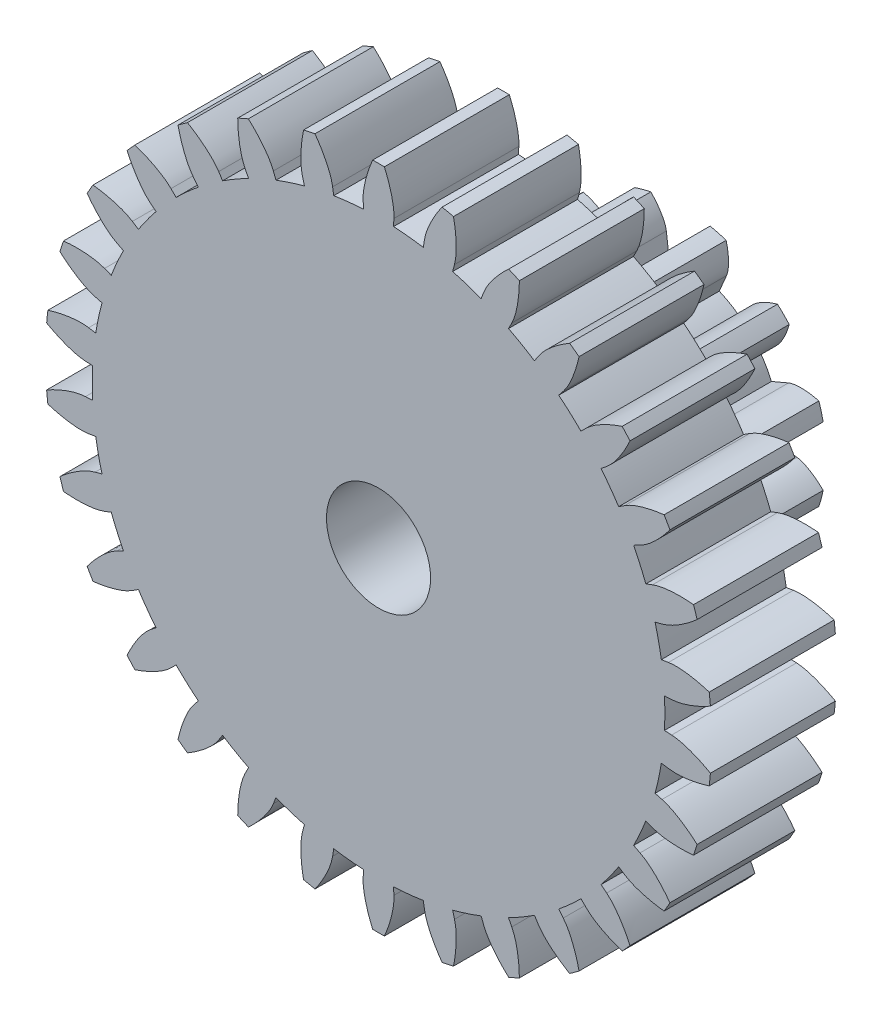
SolidWorks part; units mm, degrees
ref_plane "前视基准面" through (0, 0, 0) normal (0, 0, 1) x (1, 0, 0)
ref_plane "上视基准面" through (0, 0, 0) normal (0, 1, 0) x (1, 0, 0)
ref_plane "右视基准面" through (0, 0, 0) normal (1, 0, 0) x (0, 0, -1)
other "Configuration Table"
sketch "草图1" plane through (0, 0, 0) normal (0, 0, 1) x (1, 0, 0)
  line L0 (0, 0) -> (1.2, 0) construction
  line L1 (0, 0) -> (1.1897, 0.1566) construction
  line L2 (0, 0) -> (1.1195, 0.1354)
  line L3 (1.1897, 0.1566) -> (1.1897, -0.1566) construction
  line L4 (0, 0) -> (1.1195, -0.1354)
  circle A0 centre (0, 0) radius 1.4
  circle A1 centre (0, 0) radius 1.2 construction
  circle A2 centre (0, 0) radius 0.95
  circle A3 centre (0, 0) radius 1.1276 construction
  circle A4 centre (0, 0) radius 0.5
  spline S0 degree 4 poles (1.1195, 0.1354) (1.128, 0.1365) (1.1516, 0.1411) (1.1949, 0.157) (1.2609, 0.1921) (1.3385, 0.2504) (1.4265, 0.3386) (1.513, 0.4563) (1.5884, 0.5979) (1.6479, 0.7602) (1.6868, 0.9286) (1.7064, 1.1002) (1.7082, 1.2814) (1.6868, 1.5048) (1.6275, 1.7661) (1.5147, 2.0566) (1.3415, 2.356) (1.1264, 2.6272) (0.878, 2.867) (0.599, 3.0728) (0.3008, 3.2436) (-0.0211, 3.378) (-0.346, 3.4768) (-0.6967, 3.5387) (-0.9642, 3.5622) (-1.2659, 3.561) (-1.4376, 3.5485) (-1.6326, 3.5286) (-1.737, 3.508) (-1.8243, 3.4941) (-1.8493, 3.4877) (-1.868, 3.4841) knots 0 0 0 0 0 0.005604 0.015718 0.02996 0.048734 0.068727 0.096889 0.125051 0.153212 0.181374 0.209535 0.237696 0.271429 0.327752 0.384075 0.440398 0.496721 0.553044 0.609367 0.66569 0.722013 0.778336 0.834659 0.890982 0.909091 0.954545 0.977273 0.988636 1 1 1 1 1 construction
  spline S1 degree 4 poles (1.1195, 0.1354) (1.128, 0.1365) (1.1516, 0.1411) (1.1949, 0.157) (1.2609, 0.1921) (1.3385, 0.2504) (1.4265, 0.3386) (1.513, 0.4563) (1.5884, 0.5979) (1.6479, 0.7602) (1.6868, 0.9286) (1.7064, 1.1002) (1.7082, 1.2814) (1.6868, 1.5048) (1.6275, 1.7661) (1.5147, 2.0566) (1.3415, 2.356) (1.1264, 2.6272) (0.878, 2.867) (0.599, 3.0728) (0.3008, 3.2436) (-0.0211, 3.378) (-0.346, 3.4768) (-0.6967, 3.5387) (-0.9642, 3.5622) (-1.1881, 3.5613) (-1.292, 3.5571) (-1.3172, 3.5557) knots 0 0 0 0 0 0.005604 0.015718 0.02996 0.048734 0.068727 0.096889 0.125051 0.153212 0.181374 0.209535 0.237696 0.271429 0.327752 0.384075 0.440398 0.496721 0.553044 0.609367 0.66569 0.722013 0.778336 0.834659 0.890982 0.909091 0.909091 0.909091 0.909091 0.909091
  spline S2 degree 4 poles (1.1195, -0.1354) (1.128, -0.1365) (1.1516, -0.1411) (1.1949, -0.157) (1.2609, -0.1921) (1.3385, -0.2504) (1.4265, -0.3386) (1.513, -0.4563) (1.5884, -0.5979) (1.6479, -0.7602) (1.6868, -0.9286) (1.7064, -1.1002) (1.7082, -1.2814) (1.6868, -1.5048) (1.6275, -1.7661) (1.5147, -2.0566) (1.3415, -2.356) (1.1264, -2.6272) (0.878, -2.867) (0.599, -3.0728) (0.3008, -3.2436) (-0.0211, -3.378) (-0.346, -3.4768) (-0.6967, -3.5387) (-0.9642, -3.5622) (-1.2659, -3.561) (-1.4376, -3.5485) (-1.6326, -3.5286) (-1.737, -3.508) (-1.8243, -3.4941) (-1.8493, -3.4877) (-1.868, -3.4841) knots 0 0 0 0 0 0.005604 0.015718 0.02996 0.048734 0.068727 0.096889 0.125051 0.153212 0.181374 0.209535 0.237696 0.271429 0.327752 0.384075 0.440398 0.496721 0.553044 0.609367 0.66569 0.722013 0.778336 0.834659 0.890982 0.909091 0.954545 0.977273 0.988636 1 1 1 1 1 construction
  spline S3 degree 4 poles (1.1195, -0.1354) (1.128, -0.1365) (1.1516, -0.1411) (1.1949, -0.157) (1.2609, -0.1921) (1.3385, -0.2504) (1.4265, -0.3386) (1.513, -0.4563) (1.5884, -0.5979) (1.6479, -0.7602) (1.6868, -0.9286) (1.7064, -1.1002) (1.7082, -1.2814) (1.6868, -1.5048) (1.6275, -1.7661) (1.5147, -2.0566) (1.3415, -2.356) (1.1264, -2.6272) (0.878, -2.867) (0.599, -3.0728) (0.3008, -3.2436) (-0.0211, -3.378) (-0.346, -3.4768) (-0.6967, -3.5387) (-0.9642, -3.5622) (-1.1881, -3.5613) (-1.292, -3.5571) (-1.3172, -3.5557) knots 0 0 0 0 0 0.005604 0.015718 0.02996 0.048734 0.068727 0.096889 0.125051 0.153212 0.181374 0.209535 0.237696 0.271429 0.327752 0.384075 0.440398 0.496721 0.553044 0.609367 0.66569 0.722013 0.778336 0.834659 0.890982 0.909091 0.909091 0.909091 0.909091 0.909091
  point P15 (1.1897, 0)
  dimension "齿顶圆直径" = 2.8
  dimension "分度圆直径" = 2.4
  dimension "齿根圆直径" = 1.9
  dimension "基圆直径" = 2.2553
  dimension "内孔直径" = 1
  dimension "渐近线镜像线夹角" = 7.5
extrude "凸台-拉伸1" add sketch "草图1" along normal blind 1.7 contours A0 | A4
extrude "切除-拉伸1" cut sketch "草图1<3>" along normal through all contours A2 S3 A0 S1 region at (1.2063, 0, 0)
sketch "草图1<3>" plane through (0, 0, 0) normal (0, 0, 1) x (1, 0, 0) same geometry as "草图1"
pattern_circular "阵列(圆周)1" count 12 every 30 about axis through (0, 0, 1.7) along (0, 0, 1) of "切除-拉伸1"
sketch "草图2" plane through (0, 0, 1.7) normal (0, 0, 1) x (1, 0, 0)
  line L0 (0, 0) -> (3, 0) construction
  line L1 (0, 0) -> (2.8152, 0.1475)
  line L2 (0, 0) -> (2.8152, -0.1475)
  line L3 (2.8152, 0.1475) -> (2.8152, -0.1475) construction
  circle A0 centre (0, 0) radius 3 construction
  circle A1 centre (0, 0) radius 2.8191 construction
  circle A2 centre (0, 0) radius 2.75
  circle A3 centre (0, 0) radius 3.2
  circle A4 centre (0, 0) radius 0.5
  spline S0 degree 4 poles (2.8152, -0.1475) (2.8367, -0.1487) (2.8963, -0.1563) (3.0071, -0.1885) (3.1777, -0.2648) (3.3811, -0.397) (3.6155, -0.602) (3.8513, -0.881) (4.0635, -1.2213) (4.2394, -1.6162) (4.365, -2.0294) (4.4433, -2.4541) (4.4782, -2.9057) (4.4631, -3.4665) (4.3592, -4.1285) (4.1278, -4.8721) (3.7457, -5.6484) (3.257, -6.3614) (2.6755, -7.0016) (2.0192, -7.5623) (1.2967, -8.0391) (0.5293, -8.429) (-0.2857, -8.7309) (-1.0078, -8.9177) (-1.6623, -9.0235) (-2.1343, -9.0715) (-2.5561, -9.092) (-2.8357, -9.0955) (-3.23, -9.0889) (-3.5275, -9.0667) (-3.825, -9.0413) (-3.9743, -9.0192) (-4.0706, -9.0075) knots 0 0 0 0 0 0.005604 0.015718 0.02996 0.048734 0.068727 0.096889 0.125051 0.153212 0.181374 0.209535 0.237696 0.271429 0.327752 0.384075 0.440398 0.496721 0.553044 0.609367 0.66569 0.722013 0.778336 0.834659 0.86282 0.890982 0.909091 0.931818 0.954545 0.977273 1 1 1 1 1 construction
  spline S1 degree 4 poles (2.8152, -0.1475) (2.8367, -0.1487) (2.8963, -0.1563) (3.0071, -0.1885) (3.1777, -0.2648) (3.3811, -0.397) (3.6155, -0.602) (3.8513, -0.881) (4.0635, -1.2213) (4.2394, -1.6162) (4.365, -2.0294) (4.4433, -2.4541) (4.4782, -2.9057) (4.4631, -3.4665) (4.3592, -4.1285) (4.1278, -4.8721) (3.7457, -5.6484) (3.257, -6.3614) (2.6755, -7.0016) (2.0192, -7.5623) (1.2967, -8.0391) (0.5293, -8.429) (-0.2857, -8.7309) (-1.0078, -8.9177) (-1.6623, -9.0235) (-2.1343, -9.0715) (-2.4574, -9.0872) (-2.6182, -9.0916) (-2.6811, -9.0926) knots 0 0 0 0 0 0.005604 0.015718 0.02996 0.048734 0.068727 0.096889 0.125051 0.153212 0.181374 0.209535 0.237696 0.271429 0.327752 0.384075 0.440398 0.496721 0.553044 0.609367 0.66569 0.722013 0.778336 0.834659 0.86282 0.890982 0.909091 0.909091 0.909091 0.909091 0.909091
  spline S2 degree 4 poles (2.8152, 0.1475) (2.8367, 0.1487) (2.8963, 0.1563) (3.0071, 0.1885) (3.1777, 0.2648) (3.3811, 0.397) (3.6155, 0.602) (3.8513, 0.881) (4.0635, 1.2213) (4.2394, 1.6162) (4.365, 2.0294) (4.4433, 2.4541) (4.4782, 2.9057) (4.4631, 3.4665) (4.3592, 4.1285) (4.1278, 4.8721) (3.7457, 5.6484) (3.257, 6.3614) (2.6755, 7.0016) (2.0192, 7.5623) (1.2967, 8.0391) (0.5293, 8.429) (-0.2857, 8.7309) (-1.0078, 8.9177) (-1.6623, 9.0235) (-2.1343, 9.0715) (-2.5561, 9.092) (-2.8357, 9.0955) (-3.23, 9.0889) (-3.5275, 9.0667) (-3.825, 9.0413) (-3.9743, 9.0192) (-4.0706, 9.0075) knots 0 0 0 0 0 0.005604 0.015718 0.02996 0.048734 0.068727 0.096889 0.125051 0.153212 0.181374 0.209535 0.237696 0.271429 0.327752 0.384075 0.440398 0.496721 0.553044 0.609367 0.66569 0.722013 0.778336 0.834659 0.86282 0.890982 0.909091 0.931818 0.954545 0.977273 1 1 1 1 1 construction
  spline S3 degree 4 poles (2.8152, 0.1475) (2.8367, 0.1487) (2.8963, 0.1563) (3.0071, 0.1885) (3.1777, 0.2648) (3.3811, 0.397) (3.6155, 0.602) (3.8513, 0.881) (4.0635, 1.2213) (4.2394, 1.6162) (4.365, 2.0294) (4.4433, 2.4541) (4.4782, 2.9057) (4.4631, 3.4665) (4.3592, 4.1285) (4.1278, 4.8721) (3.7457, 5.6484) (3.257, 6.3614) (2.6755, 7.0016) (2.0192, 7.5623) (1.2967, 8.0391) (0.5293, 8.429) (-0.2857, 8.7309) (-1.0078, 8.9177) (-1.6623, 9.0235) (-2.1343, 9.0715) (-2.4574, 9.0872) (-2.6182, 9.0916) (-2.6811, 9.0926) knots 0 0 0 0 0 0.005604 0.015718 0.02996 0.048734 0.068727 0.096889 0.125051 0.153212 0.181374 0.209535 0.237696 0.271429 0.327752 0.384075 0.440398 0.496721 0.553044 0.609367 0.66569 0.722013 0.778336 0.834659 0.86282 0.890982 0.909091 0.909091 0.909091 0.909091 0.909091
  point P16 (2.8152, 0)
  dimension "内孔直径" = 1
  dimension "分度圆直径" = 6
  dimension "齿顶圆直径" = 6.4
  dimension "基圆直径" = 5.6382
  dimension "齿根圆直径" = 5.5
  dimension "渐开线镜像线夹角" = 3
extrude "凸台-拉伸2" add sketch "草图2" along normal blind 1.2 contours A3 | A4
extrude "切除-拉伸3" cut sketch "草图2<3>" along normal through all contours S3 L1 A2 L2 S1 A3 region at (2.9999, 0, 1.7)
sketch "草图2<3>" plane through (0, 0, 1.7) normal (0, 0, 1) x (1, 0, 0) same geometry as "草图2"
pattern_circular "阵列(圆周)2" count 30 over 360 about axis through (0, 0, 2.9) along (0, 0, 1) of "切除-拉伸3"
equation "\"m\"= 0.2'模数"
equation "\"z\"= 12'齿数"
equation "\"a\"= 20度'压力角"
equation "\"d\"= \"m\" * \"z\"'分度圆直径"
equation "\"da\"= ( \"z\" + 2 ) * \"m\"'齿顶圆直径"
equation "\"df\"= ( \"z\" - 2.5 ) * \"m\"'齿根圆直径"
equation "\"s\"= 0.5 * PI * \"m\"'分度圆齿厚"
equation "\"r\"= 0.38 * \"m\"'齿根圆角"
equation "\"B\"= 0.3 * \"d\"'齿厚"
equation "\"db\"= \"m\" * \"z\" * cos ( \"a\" )'基圆直径"
equation "\"rb\"= \"db\" / 2'基圆半径"
equation "\"齿顶圆直径@草图1\"= \"da\""
equation "\"分度圆直径@草图1\"= \"d\""
equation "\"齿根圆直径@草图1\"= \"df\""
equation "\"基圆直径@草图1\"= \"db\""
equation "\"渐近线镜像线夹角@草图1\"= 360 / 4 / \"z\""
equation "\"h\"= 1.7mm'齿轮厚度"
equation "\"ir\"= 1'内孔直径"
equation "\"内孔直径@草图1\"= \"ir\""
equation "\"齿轮厚@凸台-拉伸1\"= \"h\""
equation "\"齿轮夹角@阵列(圆周)1\"= 360 / \"z\""
equation "\"齿数@阵列(圆周)1\"= \"z\""
equation "\"m1\"= 0.2'模数"
equation "\"z1\"= 30'齿数"
equation "\"a1\"= 20度'压力角"
equation "\"d1\"= \"m1\" * \"z1\"'分度圆直径"
equation "\"da1\"= ( \"z1\" + 2 ) * \"m1\"'齿顶圆直径"
equation "\"df1\"= ( \"z1\" - 2.5 ) * \"m1\"'齿根圆直径"
equation "\"s1\"= 0.5 * PI * \"m1\"'分度圆齿厚"
equation "\"r1\"= 0.38 * \"m1\"'齿根圆角"
equation "\"B1\"= 0.3 * \"d1\"'齿厚"
equation "\"db1\"= \"m1\" * \"z1\" * cos ( \"a1\" )'基圆直径"
equation "\"rb1\"= \"db1\" / 2'基圆半径"
equation "\"分度圆直径@草图2\"= \"d1\""
equation "\"齿顶圆直径@草图2\"= \"da1\""
equation "\"基圆直径@草图2\"= \"db1\""
equation "\"齿根圆直径@草图2\"= \"df1\""
equation "\"渐开线镜像线夹角@草图2\"= 360 / 4 / \"z1\""
equation "\"内孔直径@草图2\"= \"ir\""
equation "\"二层齿轮厚@凸台-拉伸2\" = \"h1\""
equation "\"h1\"= 1.2'齿轮厚度"
equation "\"二层齿数@阵列(圆周)2\"= \"z1\""
